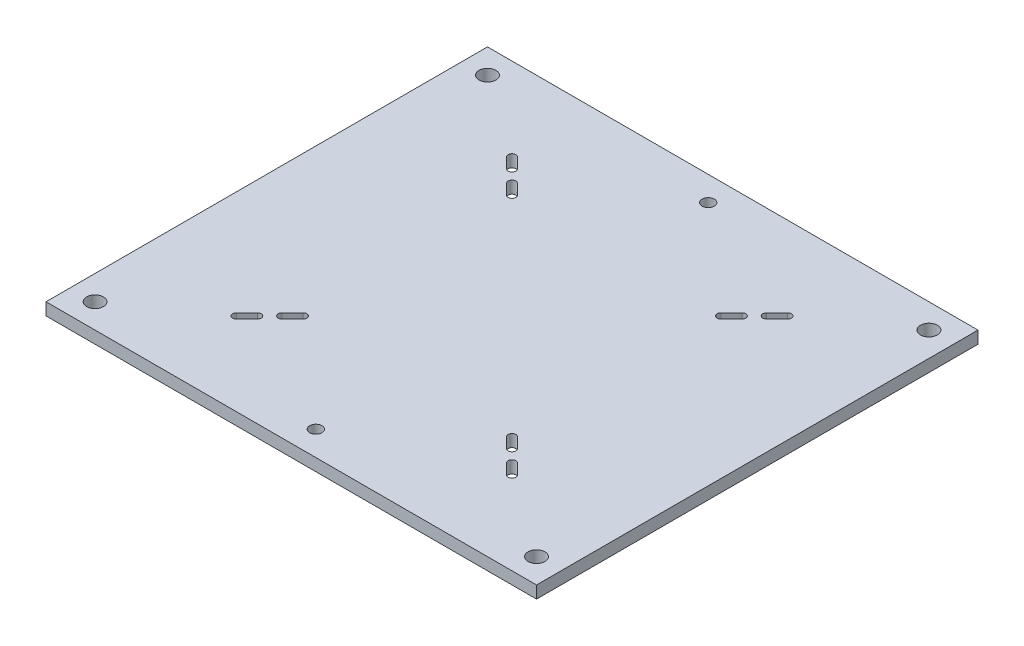
SolidWorks part; units mm, degrees
ref_plane "Front Plane" through (0, 0, 0) normal (0, 0, 1) x (1, 0, 0)
ref_plane "Top Plane" through (0, 0, 0) normal (0, 1, 0) x (1, 0, 0)
ref_plane "Right Plane" through (0, 0, 0) normal (1, 0, 0) x (0, 0, -1)
sketch "Sketch1" plane through (0, 0, 0) normal (0, 1, 0) x (1, 0, 0)
  line L1 (0, 0) -> (254, 0)
  line L2 (0, 0) -> (0, -228.6)
  line L3 (0, -228.6) -> (254, -228.6)
  line L4 (254, 0) -> (254, -228.6)
  dimension "D1" = 254
  dimension "D2" = 228.6
extrude "base plate" add sketch "Sketch1" against normal blind 6.35
sketch "center lines" plane through (0, 0, 0) normal (0, 1, 0) x (1, 0, 0)
  line L0 (127, 0) -> (127, -228.6) construction
  line L1 (254, 0) -> (0, 0) construction
  line L2 (0, -228.6) -> (254, -228.6) construction
  line L3 (0, -114.3) -> (254, -114.3) construction
  line L4 (0, 0) -> (0, -228.6) construction
  line L5 (254, -228.6) -> (254, 0) construction
sketch "Sketch3" plane through (0, 0, 0) normal (0, 1, 0) x (1, 0, 0)
  line L0 (42.875, -187.6487) -> (53.6513, -198.425)
  line L1 (53.6513, -198.425) -> (87.7763, -164.3)
  line L2 (87.7763, -164.3) -> (77, -153.5237)
  line L3 (77, -153.5237) -> (42.875, -187.6487)
  line L4 (55.6722, -185.6278) -> (61.0604, -180.2396) construction
  line L5 (54.258, -184.2135) -> (59.6462, -178.8254)
  line L6 (57.0865, -187.042) -> (62.4746, -181.6538)
  line L7 (0, -228.6) -> (254, -228.6) construction
  line L8 (72.8691, -168.4309) -> (67.4809, -173.8191) construction
  line L9 (74.2833, -169.8451) -> (68.8951, -175.2333)
  line L10 (127, 0) -> (127, -228.6) construction
  line L11 (0, -114.3) -> (254, -114.3) construction
  line L12 (87.7763, -64.3) -> (77, -75.0763)
  line L13 (53.6513, -30.175) -> (87.7763, -64.3)
  line L14 (42.875, -40.9513) -> (53.6513, -30.175)
  line L15 (77, -75.0763) -> (42.875, -40.9513)
  line L16 (200.3487, -30.175) -> (166.2237, -64.3)
  line L17 (211.125, -40.9513) -> (200.3487, -30.175)
  line L18 (177, -75.0763) -> (211.125, -40.9513)
  line L19 (166.2237, -64.3) -> (177, -75.0763)
  line L20 (166.2237, -164.3) -> (177, -153.5237)
  line L21 (200.3487, -198.425) -> (166.2237, -164.3)
  line L22 (211.125, -187.6487) -> (200.3487, -198.425)
  line L23 (177, -153.5237) -> (211.125, -187.6487)
  line L24 (71.4549, -167.0167) -> (66.0667, -172.4049)
  line L25 (55.6722, -42.9722) -> (61.0604, -48.3604) construction
  line L26 (54.258, -44.3865) -> (59.6462, -49.7746)
  line L27 (57.0865, -41.558) -> (62.4746, -46.9462)
  line L28 (72.8691, -60.1691) -> (67.4809, -54.7809) construction
  line L29 (74.2833, -58.7549) -> (68.8951, -53.3667)
  line L30 (71.4549, -61.5833) -> (66.0667, -56.1951)
  line L31 (198.3278, -42.9722) -> (192.9396, -48.3604) construction
  line L32 (199.742, -44.3865) -> (194.3538, -49.7746)
  line L33 (196.9135, -41.558) -> (191.5254, -46.9462)
  line L34 (181.1309, -60.1691) -> (186.5191, -54.7809) construction
  line L35 (179.7167, -58.7549) -> (185.1049, -53.3667)
  line L36 (182.5451, -61.5833) -> (187.9333, -56.1951)
  line L37 (181.1309, -168.4309) -> (186.5191, -173.8191) construction
  line L38 (179.7167, -169.8451) -> (185.1049, -175.2333)
  line L39 (182.5451, -167.0167) -> (187.9333, -172.4049)
  line L40 (198.3278, -185.6278) -> (192.9396, -180.2396) construction
  line L41 (199.742, -184.2135) -> (194.3538, -178.8254)
  line L42 (196.9135, -187.042) -> (191.5254, -181.6538)
  line L43 (77, -164.3) -> (77, -153.5237)
  line L44 (87.7763, -164.3) -> (77, -164.3)
  line L45 (77, -64.3) -> (77, -75.0763)
  line L46 (87.7763, -64.3) -> (77, -64.3)
  line L47 (177, -64.3) -> (177, -75.0763)
  line L48 (166.2237, -64.3) -> (177, -64.3)
  line L49 (177, -164.3) -> (177, -153.5237)
  line L50 (166.2237, -164.3) -> (177, -164.3)
  arc A0 (54.258, -184.2135) -> (57.0865, -187.042) centre (55.6722, -185.6278) ccw
  arc A1 (62.4746, -181.6538) -> (59.6462, -178.8254) centre (61.0604, -180.2396) ccw
  arc A2 (74.2833, -169.8451) -> (71.4549, -167.0167) centre (72.8691, -168.4309) ccw
  arc A3 (66.0667, -172.4049) -> (68.8951, -175.2333) centre (67.4809, -173.8191) ccw
  arc A4 (54.258, -44.3865) -> (57.0865, -41.558) centre (55.6722, -42.9722) cw
  arc A5 (62.4746, -46.9462) -> (59.6462, -49.7746) centre (61.0604, -48.3604) cw
  arc A6 (74.2833, -58.7549) -> (71.4549, -61.5833) centre (72.8691, -60.1691) cw
  arc A7 (66.0667, -56.1951) -> (68.8951, -53.3667) centre (67.4809, -54.7809) cw
  arc A8 (199.742, -44.3865) -> (196.9135, -41.558) centre (198.3278, -42.9722) ccw
  arc A9 (191.5254, -46.9462) -> (194.3538, -49.7746) centre (192.9396, -48.3604) ccw
  arc A10 (179.7167, -58.7549) -> (182.5451, -61.5833) centre (181.1309, -60.1691) ccw
  arc A11 (187.9333, -56.1951) -> (185.1049, -53.3667) centre (186.5191, -54.7809) ccw
  arc A12 (179.7167, -169.8451) -> (182.5451, -167.0167) centre (181.1309, -168.4309) cw
  arc A13 (187.9333, -172.4049) -> (185.1049, -175.2333) centre (186.5191, -173.8191) cw
  arc A14 (199.742, -184.2135) -> (196.9135, -187.042) centre (198.3278, -185.6278) cw
  arc A15 (191.5254, -181.6538) -> (194.3538, -178.8254) centre (192.9396, -180.2396) cw
  point P29 (58.3663, -182.9337)
  point P36 (70.175, -171.125)
  point P44 (58.3663, -45.6663)
  point P51 (70.175, -57.475)
  point P58 (195.6337, -45.6663)
  point P65 (183.825, -57.475)
  point P72 (183.825, -171.125)
  point P79 (195.6337, -182.9337)
  point P84 (62.4746, -178.8254)
  point P85 (66.0667, -175.2333)
  dimension "D6" = 2
  dimension "D10" = 5.08
  dimension "D9" = 5.842
  dimension "D1" = 48.26
  dimension "D2" = 15.24
  dimension "D3" = 45
  dimension "D4" = 100
  dimension "D5" = 100
  dimension "D7" = 7.62
  dimension "D8" = 7.62
extrude "slots" cut sketch "Sketch3" against normal through all contours A5 L27 A4 L26 | L33 A9 L32 A8 | L36 A11 L35 A10 | A13 L39 A12 L38 | A15 L42 A14 L41 | L6 A1 L5 A0 | L24 A3 L9 A2 | L30 A7 L29 A6 region at (58.3663, 0, 45.6663) region at (195.6337, 0, 45.6663) region at (183.825, 0, 57.475) region at (183.825, 0, 171.125) region at (195.6337, 0, 182.9337)
hole_wizard "Feet connection hole" positions "Sketch6" profile "Sketch7" hole size "1/4-20" standard "PEM® Inch" end condition through all
sketch "Sketch6" plane through (0, 0, 0) normal (0, 1, 0) x (1, 0, 0)
  line L0 (0, -228.6) -> (254, -228.6) construction
  line L1 (0, 0) -> (0, -228.6) construction
  line L2 (254, -228.6) -> (254, 0) construction
  line L3 (254, 0) -> (0, 0) construction
  point P3 (12.7, -215.9)
  point P19 (241.3, -12.7)
  point P33 (12.7, -12.7)
  point P37 (241.3, -215.9)
  dimension "D1" = 12.7
  dimension "D2" = 12.7
  dimension "D3" = 12.7
  dimension "D4" = 12.7
sketch "Sketch7" plane through (12.7, 0, 215.9) normal (1, 0, 0) x (0, 0, 1)
  line L0 (0, 0) -> (0, 6.35)
  line L1 (0, 6.35) -> (4.3688, 6.35)
  line L2 (4.3688, 6.35) -> (4.3688, 0)
  line L5 (4.3688, 0) -> (0, 0)
  line L11 (0, -6.35) -> (0, 107.95) construction
  dimension "Thru Hole Dia." = 8.7376
  dimension "Thru Hole Depth" = 6.35
hole_wizard "Hole for #10 Blind Fasteners (B,BS)1" positions "Sketch17" profile "Sketch18" hole size "#10-32" standard "PEM® Inch" end condition through all
sketch "Sketch17" plane through (0, 0, 0) normal (0, 1, 0) x (1, 0, 0)
  line L0 (0, -228.6) -> (254, -228.6) construction
  line L1 (254, 0) -> (0, 0) construction
  line L2 (254, -228.6) -> (254, 0) construction
  line L3 (0, 0) -> (0, -228.6) construction
  point P0 (127, -215.9)
  point P2 (127, -12.7)
  dimension "D1" = 12.7
  dimension "D2" = 12.7
  dimension "D3" = 127
  dimension "D4" = 127
sketch "Sketch18" plane through (127, 0, 215.9) normal (1, 0, 0) x (0, 0, 1)
  line L0 (0, 0) -> (0, 6.35)
  line L1 (0, 6.35) -> (3.175, 6.35)
  line L2 (3.175, 6.35) -> (3.175, 0)
  line L5 (3.175, 0) -> (0, 0)
  line L11 (0, -6.35) -> (0, 107.95) construction
  dimension "Thru Hole Dia." = 6.35
  dimension "Thru Hole Depth" = 6.35
